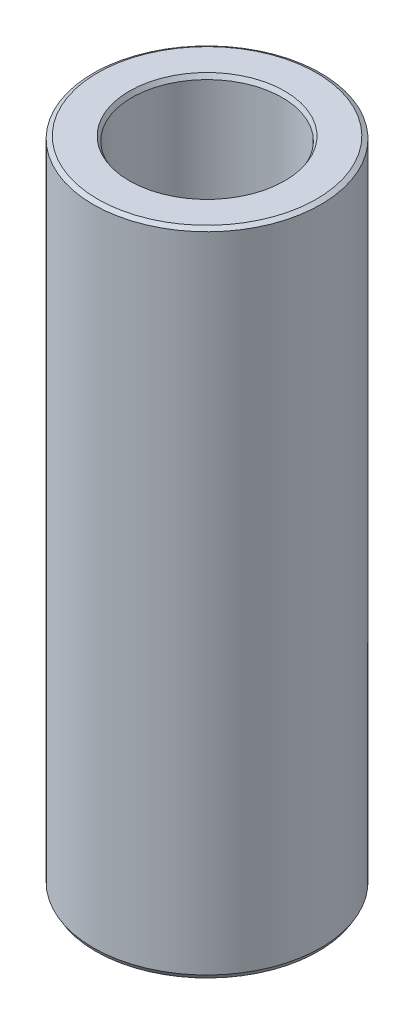
SolidWorks part; units mm, degrees
ref_plane "Front Plane" through (0, 0, 0) normal (0, 0, 1) x (1, 0, 0)
ref_plane "Top Plane" through (0, 0, 0) normal (0, 1, 0) x (1, 0, 0)
ref_plane "Right Plane" through (0, 0, 0) normal (1, 0, 0) x (0, 0, -1)
sketch "Sketch1" plane through (0, 0, 0) normal (0, 1, 0) x (1, 0, 0)
  circle A0 centre (0, 0) radius 35
  dimension "SLEEVE_OD" = 70
extrude "Boss-Extrude1" add sketch "Sketch1" along normal blind 200.0726
sketch "Sketch2" plane through (0, 0, 0) normal (0, 1, 0) x (1, 0, 0)
  circle A0 centre (0, 0) radius 23.1405
  dimension "BORE_D" = 46.2809
extrude "Cut-Extrude1" cut sketch "Sketch2" along normal through all
chamfer "Chamfer1" distance 0.7731 angle 60 4 edges at (0, 200.0726, 23.1405) (0, 0, 23.1405) (0, 0, 35) (0, 200.0726, 35) first distance on face at (0, 200.0726, 23.1405) first distance on face at (0, 0, 23.1405) first distance on face at (0, 200.0726, 35)
